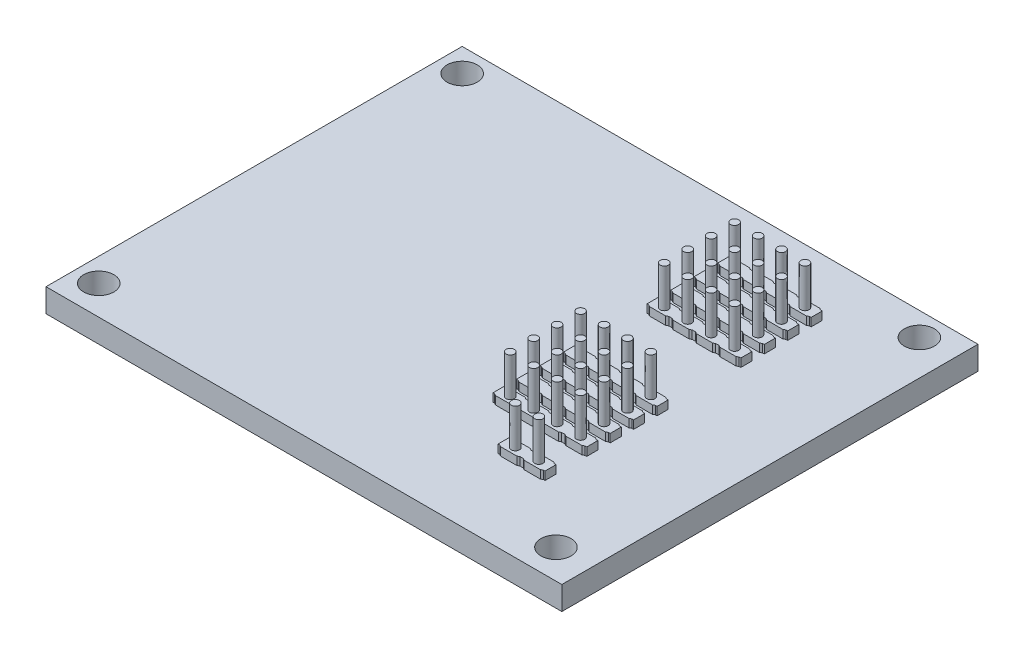
SolidWorks part; units mm, degrees
material "6061-T6 (SS)"
ref_plane "Front Plane" through (0, 0, 0) normal (0, 0, 1) x (1, 0, 0)
ref_plane "Top Plane" through (0, 0, 0) normal (0, 1, 0) x (1, 0, 0)
ref_plane "Right Plane" through (0, 0, 0) normal (1, 0, 0) x (0, 0, -1)
sketch "Sketch1" plane through (0, 0, 0) normal (0, 1, 0) x (1, 0, 0)
  line L1 (-27.94, -22.5425) -> (27.94, -22.5425)
  line L2 (-27.94, -22.5425) -> (-27.94, 22.5425)
  line L3 (-27.94, 22.5425) -> (27.94, 22.5425)
  line L4 (27.94, -22.5425) -> (27.94, 22.5425)
  line L5 (-27.94, -22.5425) -> (27.94, 22.5425) construction
  line L6 (-27.94, 22.5425) -> (27.94, -22.5425) construction
  point P0 (0, 0)
  dimension "D1" = 55.88
  dimension "D2" = 45.085
extrude "Boss-Extrude1" add sketch "Sketch1" along normal blind 2.54
hole_wizard "#4 Clearance Hole1" positions "Sketch2" profile "Sketch3" hole size "#4" standard "ANSI Inch" end condition up to next
sketch "Sketch2" plane through (0, 2.54, 0) normal (0, 1, 0) x (1, 0, 0)
  line L0 (27.94, 22.5425) -> (-27.94, 22.5425) construction
  line L1 (-27.94, 22.5425) -> (-27.94, -22.5425) construction
  point P0 (-25.4, -19.3675)
  point P2 (-25.4, 20.0025)
  point P4 (24.13, 20.0025)
  point P6 (24.13, -19.3675)
  dimension "D1" = 2.54
  dimension "D2" = 2.54
  dimension "D3" = 49.53
  dimension "D4" = 39.37
sketch "Sketch3" plane through (-25.4, 2.54, 19.3675) normal (1, 0, 0) x (0, 0, 1)
  line L0 (0, 0) -> (0, 2.54)
  line L1 (0, 2.54) -> (1.6319, 2.54)
  line L2 (1.6319, 2.54) -> (1.6319, 0)
  line L5 (1.6319, 0) -> (0, 0)
  line L11 (0, -6.35) -> (0, 107.95) construction
  dimension "Thru Hole Dia." = 3.2639
  dimension "Thru Hole Depth" = 2.54
sketch "Sketch4" plane through (0, 2.54, 0) normal (0, 1, 0) x (1, 0, 0)
  line L0 (27.94, 22.5425) -> (-27.94, 22.5425) construction
  line L1 (-27.94, 22.5425) -> (-27.94, -22.5425) construction
  circle A0 centre (16.002, 15.7353) radius 0.4445
  circle A1 centre (16.002, -0.9525) radius 0.4445
  dimension "D1" = 0.889
  dimension "D2" = 6.8072
  dimension "D3" = 43.942
  dimension "D4" = 23.495
extrude "Cut-Extrude1" cut sketch "Sketch4" against normal through all
pattern_linear "LPattern1" count 4 spacing 2.54 along (0, 0, 1) count 4 spacing 2.54 along (-1, 0, 0) of "Cut-Extrude1"
sketch "Sketch5" plane through (0, 2.54, 0) normal (0, 1, 0) x (1, 0, 0)
  circle A0 centre (16.002, -13.0845) radius 0.4445
  circle A1 centre (13.462, -13.0845) radius 0.4445
  circle A2 centre (16.002, -8.5725) radius 0.4445 construction
  point P6 (16.002, -8.5725)
  point P7 (13.462, -8.5725)
extrude "Cut-Extrude2" cut sketch "Sketch5" against normal through all
sketch "Sketch6" plane through (0, 2.54, 0) normal (0, 1, 0) x (1, 0, 0)
  line L0 (15.1229, 16.458) -> (14.918, 16.3342)
  line L1 (15.1229, 16.458) -> (16.8811, 16.458)
  line L2 (15.1229, 16.458) -> (15.1229, 15.0126)
  line L3 (15.1229, 15.0126) -> (16.8811, 15.0126)
  line L4 (16.8811, 16.458) -> (16.8811, 15.0126)
  line L5 (15.1229, 16.458) -> (16.8811, 15.0126) construction
  line L6 (15.1229, 15.0126) -> (16.8811, 16.458) construction
  line L7 (14.918, 16.3342) -> (14.732, 16.3342)
  line L8 (14.732, 16.3342) -> (14.732, 15.1364)
  line L9 (14.732, 15.1364) -> (14.918, 15.1364)
  line L10 (14.918, 15.1364) -> (15.1229, 15.0126)
  line L11 (16.002, 15.7353) -> (14.732, 15.7353) construction
  line L12 (16.002, 15.7353) -> (16.002, 15.0126) construction
  line L13 (16.8811, 16.458) -> (17.086, 16.3342)
  line L14 (16.002, 15.7353) -> (13.462, 15.7353) construction
  line L15 (14.732, 15.7353) -> (14.732, 15.1784) construction
  line L16 (17.086, 15.1364) -> (16.8811, 15.0126)
  line L17 (17.272, 15.7353) -> (17.272, 15.1784) construction
  line L18 (17.272, 15.1364) -> (17.086, 15.1364)
  line L19 (17.272, 16.3342) -> (17.272, 15.1364)
  line L20 (17.086, 16.3342) -> (17.272, 16.3342)
  point P0 (16.002, 15.7353)
  circle M18 centre (16.002, 15.7353) radius 0.4445
extrude "Boss-Extrude2" add sketch "Sketch6" along normal blind 0.889 contours L20 L13 L4 L16 L18 L19 | L4 L1 L2 L3 M18 | L9 L10 L2 L0 L7 L8 region at (14.934, 2.54, -15.7353) region at (16.002, 2.54, -16.4352) region at (17.07, 2.54, -15.7353)
pattern_linear "LPattern3" count 4 spacing 2.54 along (0, 0, 1) count 4 spacing 2.54 along (-1, 0, 0) of "Boss-Extrude2"
pattern_linear "LPattern4" count 2 spacing 16.6878 along (0, 0, 1) of "Boss-Extrude2"
pattern_linear "LPattern5" count 4 spacing 2.54 along (0, 0, 1) count 4 spacing 2.54 along (-1, 0, 0) of "LPattern4"
pattern_linear "LPattern6" count 2 spacing 28.829 along (0, 0, 1) of "Boss-Extrude2"
pattern_linear "LPattern7" count 2 spacing 2.54 along (-1, 0, 0) of "LPattern6"
sketch "Sketch7" plane through (0, 2.54, 0) normal (0, 1, 0) x (1, 0, 0)
  circle A0 centre (16.002, 15.7353) radius 0.4445
  circle A1 centre (16.002, 15.7353) radius 0.4445 construction
  circle A2 centre (13.462, 15.7353) radius 0.4445
  circle A3 centre (10.922, 15.7353) radius 0.4445
  circle A4 centre (8.382, 15.7353) radius 0.4445
  circle A5 centre (8.382, 13.1953) radius 0.4445
  circle A6 centre (10.922, 13.1953) radius 0.4445
  circle A7 centre (13.462, 13.1953) radius 0.4445
  circle A8 centre (16.002, 13.1953) radius 0.4445
  circle A9 centre (16.002, 10.6553) radius 0.4445
  circle A10 centre (13.462, 10.6553) radius 0.4445
  circle A11 centre (10.922, 10.6553) radius 0.4445
  circle A12 centre (8.382, 10.6553) radius 0.4445
  circle A13 centre (8.382, 8.1153) radius 0.4445
  circle A14 centre (10.922, 8.1153) radius 0.4445
  circle A15 centre (13.462, 8.1153) radius 0.4445
  circle A16 centre (16.002, 8.1153) radius 0.4445
  circle A17 centre (16.002, -0.9525) radius 0.4445
  circle A18 centre (16.002, -3.4925) radius 0.4445
  circle A19 centre (16.002, -6.0325) radius 0.4445
  circle A20 centre (16.002, -8.5725) radius 0.4445
  circle A21 centre (13.462, -0.9525) radius 0.4445
  circle A22 centre (13.462, -3.4925) radius 0.4445
  circle A23 centre (13.462, -6.0325) radius 0.4445
  circle A24 centre (13.462, -8.5725) radius 0.4445
  circle A25 centre (10.922, -8.5725) radius 0.4445
  circle A26 centre (10.922, -6.0325) radius 0.4445
  circle A27 centre (10.922, -3.4925) radius 0.4445
  circle A28 centre (10.922, -0.9525) radius 0.4445
  circle A29 centre (8.382, -0.9525) radius 0.4445
  circle A30 centre (8.382, -3.4925) radius 0.4445
  circle A31 centre (8.382, -6.0325) radius 0.4445
  circle A32 centre (8.382, -8.5725) radius 0.4445
  circle A33 centre (16.002, -13.0937) radius 0.4445
  circle A34 centre (13.462, -13.0937) radius 0.4445
extrude "Boss-Extrude3" add sketch "Sketch7" along normal blind 5.08 and the other way blind 5.08
